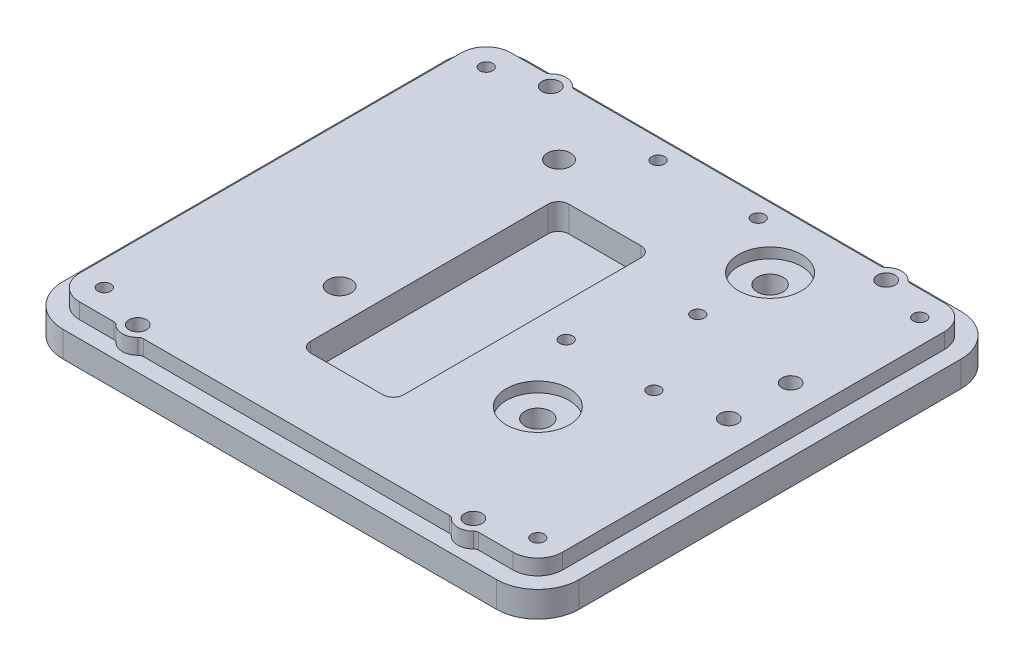
SolidWorks part; units mm, degrees
ref_plane "Front Plane" through (0, 0, 0) normal (0, 0, 1) x (1, 0, 0)
ref_plane "Top Plane" through (0, 0, 0) normal (0, 1, 0) x (1, 0, 0)
ref_plane "Right Plane" through (0, 0, 0) normal (1, 0, 0) x (0, 0, -1)
sketch "Sketch1" plane through (0, 0, 0) normal (0, 1, 0) x (1, 0, 0)
  line L1 (-50, 45) -> (50, 45)
  line L2 (-50, 45) -> (-50, -45)
  line L3 (-50, -45) -> (50, -45)
  line L4 (50, 45) -> (50, -45)
  line L5 (-50, 45) -> (50, -45) construction
  line L6 (-50, -45) -> (50, 45) construction
  point P0 (0, 0)
  dimension "D1" = 100
  dimension "D2" = 90
extrude "Boss-Extrude1" add sketch "Sketch1" along normal blind 8
fillet "Fillet1" radius 8 4 edges at (50, 4, 45) (50, 4, -45) (-50, 4, -45) (-50, 4, 45)
sketch "Sketch6" plane through (0, 8, 0) normal (0, 1, 0) x (1, 0, 0)
  line L0 (20, 30) -> (20, -15) construction
  line L1 (-42, -45) -> (42, -45) construction
  line L2 (50, -37) -> (50, 37) construction
  circle A0 centre (20, 30) radius 6.1
  circle A1 centre (20, -15) radius 6.1
  dimension "D1" = 12.2
  dimension "D2" = 45
  dimension "D3" = 30
  dimension "D4" = 30
extrude "Cut-Extrude1" cut sketch "Sketch6" against normal blind 2
sketch "Sketch7" plane through (0, 8, 0) normal (0, 1, 0) x (1, 0, 0)
  line L4 (-42, -41.8) -> (42, -41.8)
  line L5 (-42, -41.8) -> (42, -41.8)
  line L6 (42, 41.8) -> (-42, 41.8)
  line L7 (42, 41.8) -> (-42, 41.8)
  line L24 (46.8, -37) -> (46.8, 37)
  line L26 (46.8, -37) -> (46.8, 37)
  line L30 (-46.8, 37) -> (-46.8, -37)
  line L31 (-46.8, 37) -> (-46.8, -37)
  arc A8 (42, -41.8) -> (46.8, -37) centre (42, -37) ccw
  arc A20 (42, -41.8) -> (46.8, -37) centre (42, -37) ccw
  arc A24 (46.8, 37) -> (42, 41.8) centre (42, 37) ccw
  arc A26 (46.8, 37) -> (42, 41.8) centre (42, 37) ccw
  arc A28 (-42, 41.8) -> (-46.8, 37) centre (-42, 37) ccw
  arc A29 (-42, 41.8) -> (-46.8, 37) centre (-42, 37) ccw
  arc A30 (-46.8, -37) -> (-42, -41.8) centre (-42, -37) ccw
  arc A31 (-46.8, -37) -> (-42, -41.8) centre (-42, -37) ccw
  dimension "D1" = 3.2
extrude "Cut-Extrude2" cut sketch "Sketch7" against normal blind 3 flip side to cut
hole_wizard "M3x0.5 Tapped Hole1" positions "Sketch8" profile "Sketch9" tap size "M3x0.5" standard "ANSI Metric" end condition through all
sketch "Sketch8" plane through (0, 8, 0) normal (0, 1, 0) x (1, 0, 0)
  line L4 (42, 45) -> (-42, 45) construction
  point P18 (-42, -37)
  point P21 (-42, 37)
  point P24 (42, 37)
  point P27 (42, -37)
  point P30 (-9.7, 38)
  point P33 (9.7, 38)
  point P42 (20, 16)
  point P48 (28.5, -1)
  point P51 (11.5, -1)
  point P77 (0, 0)
  point P78 (20, 16)
  point P80 (11.5, -1)
  point P82 (0, 0)
  dimension "D6" = 7
sketch "Sketch9" plane through (-42, 8, 37) normal (1, 0, 0) x (0, 0, 1)
  line L0 (0, 0) -> (0, 8)
  line L1 (0, 8) -> (1.25, 8)
  line L2 (1.25, 8) -> (1.25, 0)
  line L5 (1.25, 0) -> (0, 0)
  line L11 (0, -6.35) -> (0, 107.95) construction
  dimension "Thru Tap Drill Dia." = 2.5
  dimension "Thru Tap Drill Depth" = 8
cosmetic thread "Hole Thread15" parameters "D2"=3
cosmetic thread "Hole Thread18" parameters "D2"=3
cosmetic thread "Hole Thread29" parameters "D2"=3
cosmetic thread "Hole Thread30" parameters "D2"=3
cosmetic thread "Hole Thread32" parameters "D2"=3
cosmetic thread "Hole Thread36" parameters "D2"=3
cosmetic thread "Hole Thread39" parameters "D2"=3
cosmetic thread "Hole Thread43" parameters "D2"=3
cosmetic thread "Hole Thread44" parameters "D2"=3
hole_wizard "M6x1.0 Tapped Hole2" positions "Sketch10" profile "Sketch11" tap size "M6x1.0" standard "ANSI Metric" end condition through all
sketch "Sketch10" plane through (0, 8, 0) normal (0, 1, 0) x (1, 0, 0)
  point P0 (20, 30)
  point P3 (20, -15)
sketch "Sketch11" plane through (20, 8, -30) normal (1, 0, 0) x (0, 0, 1)
  line L0 (0, 0) -> (0, 8)
  line L1 (0, 8) -> (2.5, 8)
  line L2 (2.5, 8) -> (2.5, 0)
  line L5 (2.5, 0) -> (0, 0)
  line L11 (0, -6.35) -> (0, 107.95) construction
  dimension "Thru Tap Drill Dia." = 5
  dimension "Thru Tap Drill Depth" = 8
cosmetic thread "Hole Thread11" parameters "D2"=6
cosmetic thread "Hole Thread12" parameters "D2"=6
sketch "Sketch12" plane through (0, 8, 0) normal (0, 1, 0) x (1, 0, 0)
  line L0 (-32.5, 40) -> (32.5, 40) construction
  line L1 (32.5, 40) -> (32.5, -40) construction
  line L2 (32.5, -40) -> (-32.5, -40) construction
  line L3 (-32.5, -40) -> (-32.5, 40) construction
  line L4 (42, 45) -> (-42, 45) construction
  line L5 (-42, -45) -> (42, -45) construction
  line L6 (-50, 37) -> (-50, -37) construction
  line L7 (50, -37) -> (50, 37) construction
  circle A0 centre (-32.5, 40) radius 1.6608
  circle A1 centre (-32.5, 40) radius 3
  circle A3 centre (32.5, 40) radius 3
  circle A5 centre (-32.5, -40) radius 3
  circle A7 centre (32.5, -40) radius 3
  circle A8 centre (32.5, 40) radius 1.6608
  circle A9 centre (32.5, -40) radius 1.6608
  circle A10 centre (-32.5, -40) radius 1.6608
  dimension "D1" = 6
  dimension "D2" = 5
  dimension "D3" = 5
  dimension "D4" = 17.5
  dimension "D5" = 17.5
extrude "Boss-Extrude2" add sketch "Sketch12" against normal up to surface (3 mm away) up to face at (0, 5, 0)
hole_wizard "CBORE for M3 SHCS1" positions "Sketch13" profile "Sketch14" counterbore size "M3" standard "ANSI Metric" end condition through all
sketch "Sketch13" plane through (0, 0, 0) normal (0, -1, 0) x (-1, 0, 0)
  line L0 (-20, 30) -> (-20, -15) construction
  line L2 (-20, 7.5) -> (-77.5775, 7.5) construction
  line L4 (-50, -37) -> (-50, 37) construction
  point P0 (32.5, -40)
  point P3 (-32.5, -40)
  point P6 (32.5, 40)
  point P9 (-32.5, 40)
  point P12 (-40.5, 1.5)
  point P15 (-40.5, 13.5)
  dimension "D1" = 12
  dimension "D2" = 6
  dimension "D3" = 9.5
sketch "Sketch14" plane through (-32.5, 0, 40) normal (1, 0, 0) x (0, 0, -1)
  line L0 (0, 0) -> (0, 8)
  line L1 (0, 8) -> (1.7, 8)
  line L3 (1.7, 8) -> (1.7, 3)
  line L4 (1.7, 3) -> (3.25, 3)
  line L5 (3.25, 3) -> (3.25, 0)
  line L7 (3.25, 0) -> (0, 0)
  line L11 (0, -6.35) -> (0, 107.95) construction
  dimension "Thru Hole Dia." = 3.4
  dimension "Thru Hole Depth" = 8
  dimension "C'Bore Dia." = 6.5
  dimension "C'Bore Depth" = 3
fillet "Fillet2" radius 1 8 edges at (-30.1, 6.5, -41.8) (-34.9, 6.5, -41.8) (34.9, 6.5, -41.8) (30.1, 6.5, -41.8) (34.9, 6.5, 41.8) (30.1, 6.5, 41.8) (-30.1, 6.5, 41.8) (-34.9, 6.5, 41.8)
sketch "Sketch15" plane through (0, 8, 0) normal (0, 1, 0) x (1, 0, 0)
  line L1 (-13, 22) -> (5, 22)
  line L2 (-13, 22) -> (-13, -28)
  line L3 (-13, -28) -> (5, -28)
  line L4 (5, 22) -> (5, -28)
  line L5 (-50, 37) -> (-50, -37) construction
  line L6 (-42, -45) -> (42, -45) construction
  dimension "D1" = 18
  dimension "D2" = 50
  dimension "D3" = 17
  dimension "D4" = 37
extrude "Cut-Extrude3" cut sketch "Sketch15" against normal blind 5
fillet "Fillet3" radius 2 4 edges at (-13, 5.5, 28) (5, 5.5, 28) (5, 5.5, -22) (-13, 5.5, -22)
hole_wizard "CBORE for M4 SHCS1" positions "Sketch16" profile "Sketch17" counterbore size "M4" standard "ANSI Metric" end condition through all
sketch "Sketch16" plane through (0, 0, 0) normal (0, -1, 0) x (-1, 0, 0)
  point P0 (19.4, -14)
  point P3 (19.4, 28.5)
sketch "Sketch17" plane through (-19.4, 0, 14) normal (1, 0, 0) x (0, 0, -1)
  line L0 (0, 0) -> (0, 8)
  line L1 (0, 8) -> (2.25, 8)
  line L3 (2.25, 8) -> (2.25, 4)
  line L4 (2.25, 4) -> (4, 4)
  line L5 (4, 4) -> (4, 0)
  line L7 (4, 0) -> (0, 0)
  line L11 (0, -6.35) -> (0, 107.95) construction
  dimension "Thru Hole Dia." = 4.5
  dimension "Thru Hole Depth" = 8
  dimension "C'Bore Dia." = 8
  dimension "C'Bore Depth" = 4
